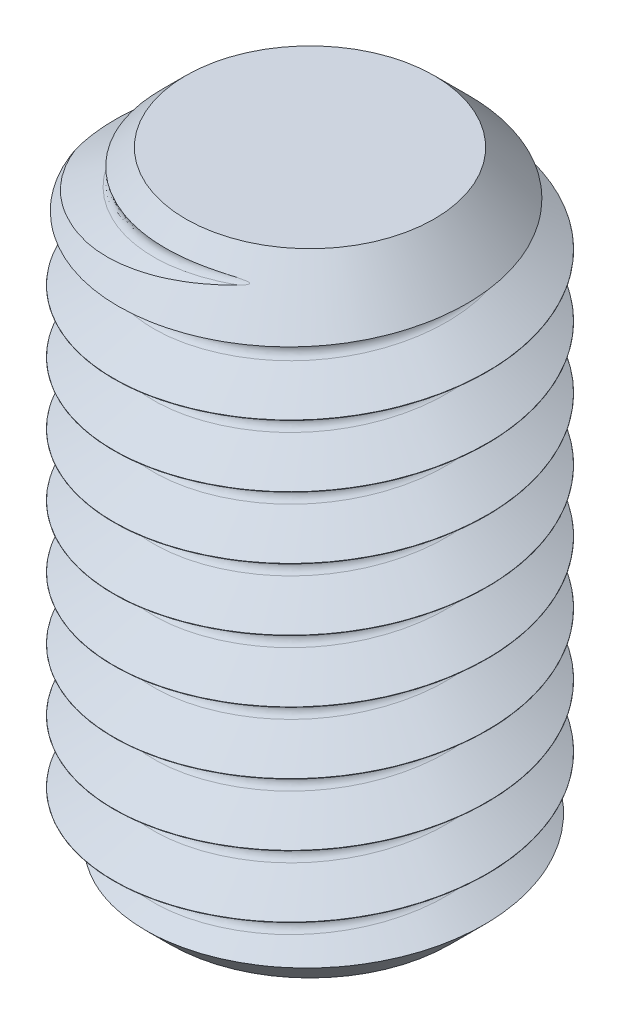
SolidWorks part; units mm, degrees
ref_plane "Front Plane" through (0, 0, 0) normal (0, 0, 1) x (1, 0, 0)
ref_plane "Top Plane" through (0, 0, 0) normal (0, 1, 0) x (1, 0, 0)
ref_plane "Right Plane" through (0, 0, 0) normal (1, 0, 0) x (0, 0, -1)
sketch "Sketch1" plane through (0, 0, 0) normal (0, 1, 0) x (1, 0, 0)
  circle A0 centre (0, 0) radius 1.5
  dimension "D1" = 3
extrude "Boss-Extrude1" add sketch "Sketch1" along normal mid plane 5.62
sketch "Sketch2" plane through (0, 0, 0) normal (0, 0, 1) x (1, 0, 0)
  line L0 (0.375, 2.81) -> (2.5874, 0.5976)
  line L1 (2.5874, 0.5976) -> (2.5874, -1.3476)
  line L2 (2.5874, -1.3476) -> (1.125, -2.81)
  line L3 (1.125, -2.81) -> (1.125, -3.9071)
  line L4 (1.125, -3.9071) -> (2.7606, -3.9071)
  line L5 (2.7606, -3.9071) -> (2.7606, 3.3192)
  line L6 (2.7606, 3.3192) -> (0.375, 3.3192)
  line L7 (0.375, 3.3192) -> (0.375, 2.81)
  line L8 (0, 0) -> (0, -3.1523) construction
  line L9 (1.5, 2.81) -> (-1.5, 2.81) construction
  line L10 (-1.5, -2.81) -> (1.5, -2.81) construction
  dimension "D1" = 0.75
  dimension "D2" = 2.25
  dimension "D3" = 135
  dimension "D4" = 135
revolve "Cut-Revolve1" cut sketch "Sketch2" angle 360 about L8
sketch "Sketch3" plane through (0, -2.81, 0) normal (0, -1, 0) x (1, 0, 0)
  line L1 (0.775, -0.4474) -> (0.775, 0.4474)
  line L2 (0.775, 0.4474) -> (0, 0.8949)
  line L3 (0, 0.8949) -> (-0.775, 0.4474)
  line L4 (-0.775, 0.4474) -> (-0.775, -0.4474)
  line L5 (-0.775, -0.4474) -> (0, -0.8949)
  line L6 (0, -0.8949) -> (0.775, -0.4474)
  circle A0 centre (0, 0) radius 0.775 construction
  dimension "D1" = 1.55
extrude "Cut-Extrude1" cut sketch "Sketch3" against normal blind 1.5
sketch "Sketch4" plane through (0, -2.81, 0) normal (0, -1, 0) x (1, 0, 0)
  circle A0 centre (0, 0) radius 1.5 construction
  circle A1 centre (0, 0) radius 1.5
curve "Helix/Spiral1" pitch 0.5 height 6 turns 12
sketch "Sketch5" plane through (0, 0, 0) normal (0, 0, 1) x (1, 0, 0)
  line L1 (1.5018, -2.5912) -> (1.1779, -2.7783)
  line L2 (1.1779, -2.9032) -> (1.5018, -3.0902)
  line L3 (1.5018, -3.0902) -> (1.5018, -2.5912)
  circle A0 centre (1.3577, -2.8407) radius 0.144 construction
  arc A1 (1.1779, -2.7783) -> (1.1779, -2.9032) centre (1.2139, -2.8407) ccw
  dimension "D2" = 0.0722
  dimension "D1" = 0.499
sweep "Cut-Sweep1" cut profiles "Sketch5" path "Helix/Spiral1" align with end faces yes
sketch "Sketch6" plane through (0, -2.81, 0) normal (0, -1, 0) x (1, 0, 0)
  circle A0 centre (0, 0) radius 0.8949
extrude "Cut-Extrude2" cut sketch "Sketch6" against normal blind 1 draft 75
sketch "Sketch7" plane through (0, 0, 0) normal (0, 0, 1) x (1, 0, 0)
  line L0 (-1, 2.185) -> (1, 2.185)
  line L1 (-0.375, 2.81) -> (-1.2003, 1.9847) construction
  line L2 (1.3588, 1.8262) -> (0.375, 2.81) construction
  line L3 (1, 2.185) -> (1, 3.8433)
  line L4 (1, 3.8433) -> (-1, 3.8433)
  line L5 (-1, 3.8433) -> (-1, 2.185)
  dimension "D1" = 2
extrude "Cut-Extrude3" cut sketch "Sketch7" against normal through all both and the other way through all
sketch "Sketch8" plane through (0, 0, 0) normal (0, 0, 1) x (1, 0, 0)
  line L0 (0, 2.185) -> (0, -2.81) construction
  line L1 (1, 2.185) -> (-1, 2.185) construction
  line L2 (-1.125, -2.81) -> (1.125, -2.81) construction
